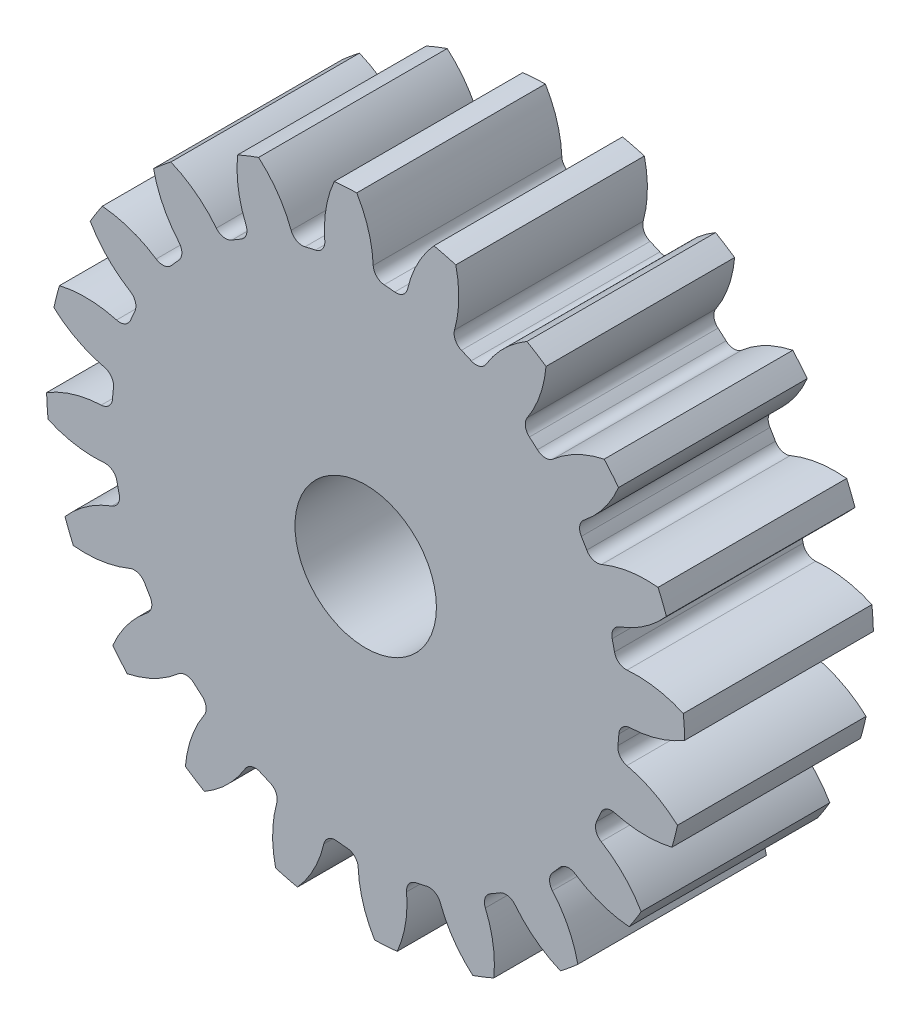
SolidWorks part; units mm, degrees
ref_plane "Front" through (0, 0, 0) normal (0, 0, 1) x (1, 0, 0)
ref_plane "Top" through (0, 0, 0) normal (0, 1, 0) x (1, 0, 0)
ref_plane "Right" through (0, 0, 0) normal (1, 0, 0) x (0, 0, -1)
sketch "Sketch3" plane through (0, 0, 0) normal (0, 0, 1) x (1, 0, 0)
  circle A0 centre (0, 0) radius 10.7462
  dimension "od" = 21.4923
extrude "gearBody" add sketch "Sketch3" along normal blind 6.35
sketch "Sketch2" plane through (0, 0, 0) normal (0, 0, 1) x (1, 0, 0)
  line L0 (0, 0) -> (8.7381, 3.6194) construction
  line L1 (11.4643, -3.634) -> (0, 0) construction
  line L2 (0, 0) -> (36.3143, 0) construction
  line L3 (9.7685, -0.1174) -> (9.6195, -1.704) construction
  line L5 (9.694, -0.9107) -> (0, 0) construction
  line L7 (0, 0) -> (9.4581, 0) construction
  arc A0 (9.4562, -0.1898) -> (9.3261, -1.5747) centre (0, 0) ccw construction
  arc A1 (10.7419, 0.3012) -> (10.4979, -2.2966) centre (0, 0) ccw construction
  arc A2 (9.7685, -0.1174) -> (9.6195, -1.704) centre (0, 0) ccw construction
  arc A3 (8.49, -0.9775) -> (8.5235, -0.6209) centre (0, 0) ccw
  arc A4 (11.4643, -3.634) -> (8.7938, -1.409) centre (7.9111, -5.1835) ccw
  arc A5 (11.4643, -3.634) -> (11.9405, 1.4352) centre (0, 0) ccw
  arc A6 (11.9405, 1.4352) -> (8.9023, -0.2534) centre (8.7381, 3.6194) cw
  arc A7 (8.5235, -0.6209) -> (8.9023, -0.2534) centre (8.9191, -0.6497) cw
  arc A8 (8.7938, -1.409) -> (8.49, -0.9775) centre (8.8841, -1.0228) cw
  point P6 (11.9405, 1.4352)
  point P22 (11.4643, -3.634)
  dimension "baseDia" = 18.9161
  dimension "od" = 21.4923
  dimension "pd" = 19.5385
  dimension "rd" = 17.0922
  dimension "rFillet" = 0.3966
  dimension "pointX" = 11.9405
  dimension "pointY" = 1.4352
  dimension "CTT" = 1.5865
  dimension "flankCenterAngle" = 22.5
extrude "toothCut" cut sketch "Sketch2" along normal through all
pattern_circular "CirPattern1" count 20 over 360 about axis through (0, 0, 6.35) along (0, 0, -1) of "toothCut"
ref_axis "toothSpace" through (0, 0, 0) along (0.9956, -0.0935, 0)
ref_axis "Axis2" through (10.4101, -2.6664, 0) along (-0.9687, 0.2481, 0)
sketch "hub1Dia" plane through (0, 0, 0) normal (0, 0, -1) x (-1, 0, 0)
  circle A0 centre (0, 0) radius 12.7
  dimension "hub1Dia" = 25.4
sketch "hub2Dia" plane through (0, 0, 6.35) normal (0, 0, 1) x (1, 0, 0)
  circle A0 centre (0, 0) radius 12.7
  dimension "hub2dia" = 25.4
sketch "boreDia" plane through (0, 0, 0) normal (0, 0, 1) x (1, 0, 0)
  circle A0 centre (0, 0) radius 2.3812
  dimension "boreDia" = 4.7625
extrude "bore" cut sketch "boreDia" against normal mid plane 25400
sketch "kwy1sketch" plane through (0, 0, 0) normal (0, 0, 1) x (1, 0, 0)
  line L0 (-6.0081, 1.2078) -> (0, 0) construction
  line L1 (29.7394, 6.9755) -> (24.7333, -17.9263)
  line L2 (24.7333, -17.9263) -> (-6.394, -11.6687)
  line L3 (29.7394, 6.9755) -> (-1.3879, 13.2331)
  line L4 (-6.394, -11.6687) -> (0, 0)
  line L5 (0, 0) -> (-1.3879, 13.2331)
  line L6 (0, 0) -> (8.5087, -0.7993) construction
  line L7 (27.2363, -5.4754) -> (0, 0) construction
  arc A7 (8.49, -0.9775) -> (8.5235, -0.6209) centre (0, 0) ccw construction
  point P9 (27.2363, -5.4754)
  point P13 (-1.0022, 0.2015)
  dimension "kwy1width" = 25.4
  dimension "kwy1depth" = 27.7812
  dimension "kwy1angle" = 6
  dimension "kwy1Depth2" = 31.75
sketch "kwy2sketch" plane through (0, 0, 0) normal (0, 0, 1) x (1, 0, 0)
  line L0 (8.5087, -0.7993) -> (0, 0) construction
  line L1 (0, 0) -> (-3.526, -2.3456) construction
  line L2 (16.0965, 25.9613) -> (30.1649, 4.8132)
  line L3 (30.1649, 4.8132) -> (3.7298, -12.7722)
  line L4 (16.0965, 25.9613) -> (-10.3386, 8.3759)
  line L5 (3.7298, -12.7722) -> (0, 0)
  line L6 (0, 0) -> (-10.3386, 8.3759)
  arc A2 (8.49, -0.9775) -> (8.5235, -0.6209) centre (0, 0) ccw construction
  point P10 (23.1307, 15.3873)
  dimension "kwy2angle" = 39
  dimension "kwy2Width" = 25.4
  dimension "kwy2depth" = 27.7812
  dimension "kwy2Depth2" = 31.75
sketch "kwy3sketch" plane through (0, 0, 0) normal (0, 0, 1) x (1, 0, 0)
  line L0 (8.5087, -0.7993) -> (0, 0) construction
  line L1 (0, 0) -> (-0.6038, -3.0037) construction
  line L2 (-6.9755, 29.7394) -> (17.9263, 24.7333)
  line L3 (17.9263, 24.7333) -> (11.6687, -6.394)
  line L4 (-6.9755, 29.7394) -> (-13.2331, -1.3879)
  line L5 (11.6687, -6.394) -> (0, 0)
  line L6 (-13.2331, -1.3879) -> (0, 0)
  point P10 (5.4754, 27.2363)
  dimension "kwy3angle" = 84
  dimension "kwy3depth" = 27.7812
  dimension "kwy3width" = 25.4
  dimension "kwy3Depth2" = 31.75
sketch "kwy4sketch" plane through (0, 0, 0) normal (0, 0, 1) x (1, 0, 0)
  line L0 (8.5087, -0.7993) -> (0, 0) construction
  line L1 (0, 0) -> (1.3268, -1.9945) construction
  line L2 (-4.8132, 30.1649) -> (-25.9613, 16.0965)
  line L3 (-25.9613, 16.0965) -> (-8.3759, -10.3386)
  line L4 (-8.3759, -10.3386) -> (0, 0)
  line L5 (12.7722, 3.7298) -> (0, 0)
  line L6 (-4.8132, 30.1649) -> (12.7722, 3.7298)
  point P15 (-15.3873, 23.1307)
  dimension "kwy4angle" = 129
  dimension "kwy4depth" = 27.7812
  dimension "kwy4width" = 25.4
  dimension "kwy4Depth2" = 31.75
sketch "kwy5sketch" plane through (0, 0, 0) normal (0, 0, 1) x (1, 0, 0)
  line L0 (8.5087, -0.7993) -> (0, 0) construction
  line L1 (0, 0) -> (2.017, -0.4055) construction
  line L2 (-24.7333, 17.9263) -> (-29.7394, -6.9755)
  line L3 (-29.7394, -6.9755) -> (1.3879, -13.2331)
  line L4 (-24.7333, 17.9263) -> (6.394, 11.6687)
  line L5 (1.3879, -13.2331) -> (0, 0)
  line L6 (6.394, 11.6687) -> (0, 0)
  point P10 (-27.2363, 5.4754)
  dimension "kwy5width" = 25.4
  dimension "kwy5depth" = 27.7812
  dimension "kwy5angle" = 174
  dimension "kwy5Depth2" = 31.75
sketch "kwy6sketch" plane through (0, 0, 0) normal (0, 0, 1) x (1, 0, 0)
  line L0 (8.5087, -0.7993) -> (0, 0) construction
  line L1 (0, 0) -> (1.7116, 1.1386) construction
  line L2 (-30.1649, -4.8132) -> (-16.0965, -25.9613)
  line L3 (-16.0965, -25.9613) -> (10.3386, -8.3759)
  line L4 (-30.1649, -4.8132) -> (-3.7298, 12.7722)
  line L5 (10.3386, -8.3759) -> (0, 0)
  line L6 (-3.7298, 12.7722) -> (0, 0)
  point P10 (-23.1307, -15.3873)
  dimension "kwy6angle" = 219
  dimension "kwy6width" = 25.4
  dimension "kwy6depth" = 27.7812
  dimension "kwy6Depth2" = 31.75
sketch "kwy7sketch" plane through (0, 0, 0) normal (0, 0, 1) x (1, 0, 0)
  line L0 (8.5087, -0.7993) -> (0, 0) construction
  line L1 (0, 0) -> (0.4539, 2.2579) construction
  line L2 (-17.9263, -24.7333) -> (6.9755, -29.7394)
  line L3 (-17.9263, -24.7333) -> (-11.6687, 6.394)
  line L4 (6.9755, -29.7394) -> (13.2331, 1.3879)
  line L5 (-11.6687, 6.394) -> (0, 0)
  line L6 (13.2331, 1.3879) -> (0, 0)
  point P10 (-5.4754, -27.2363)
  dimension "kwy7angle" = 84
  dimension "kwy7width" = 25.4
  dimension "kwy7depth" = 27.7812
  dimension "kwy7angle1" = 264
  dimension "kwy7Depth2" = 31.75
sketch "kwy8sketch" plane through (0, 0, 0) normal (0, 0, 1) x (1, 0, 0)
  line L0 (8.5087, -0.7993) -> (0, 0) construction
  line L1 (0, 0) -> (-1.1333, 1.7036) construction
  line L2 (4.8132, -30.1649) -> (25.9613, -16.0965)
  line L3 (25.9613, -16.0965) -> (8.3759, 10.3386)
  line L4 (4.8132, -30.1649) -> (-12.7722, -3.7298)
  line L5 (8.3759, 10.3386) -> (0, 0)
  line L6 (-12.7722, -3.7298) -> (0, 0)
  point P10 (15.3873, -23.1307)
  dimension "kwy8angle" = 309
  dimension "kwy8width" = 25.4
  dimension "kwy8depth" = 27.7812
  dimension "kwy8Depth2" = 31.75
sketch "centerLine" plane through (0, 0, 0) normal (0, 1, 0) x (1, 0, 0)
  line L0 (0, 36.4807) -> (0, -59.6309) construction
ref_plane "CB1plane" through (0, 0, 0) normal (0, 0, -1) x (-1, 0, 0)
sketch "CB1diameter" plane through (0, 0, 0) normal (0, 0, -1) x (-1, 0, 0)
  circle A0 centre (0, 0) radius 12.7
  dimension "CB1diameter" = 25.4
ref_plane "CB2plane" through (0, 0, 6.35) normal (0, 0, 1) x (1, 0, 0)
sketch "CB2diameter" plane through (0, 0, 6.35) normal (0, 0, 1) x (1, 0, 0)
  circle A0 centre (0, 0) radius 12.7
  dimension "CB2diameter" = 25.4
ref_axis "Axis1" through (0, 0, 50) along (0, 0, -1)
sketch "Sketch4" plane through (0, 0, 6.35) normal (0, 0, 1) x (1, 0, 0)
  circle A0 centre (0, 0) radius 9.7663
  dimension "D1" = 19.5326
